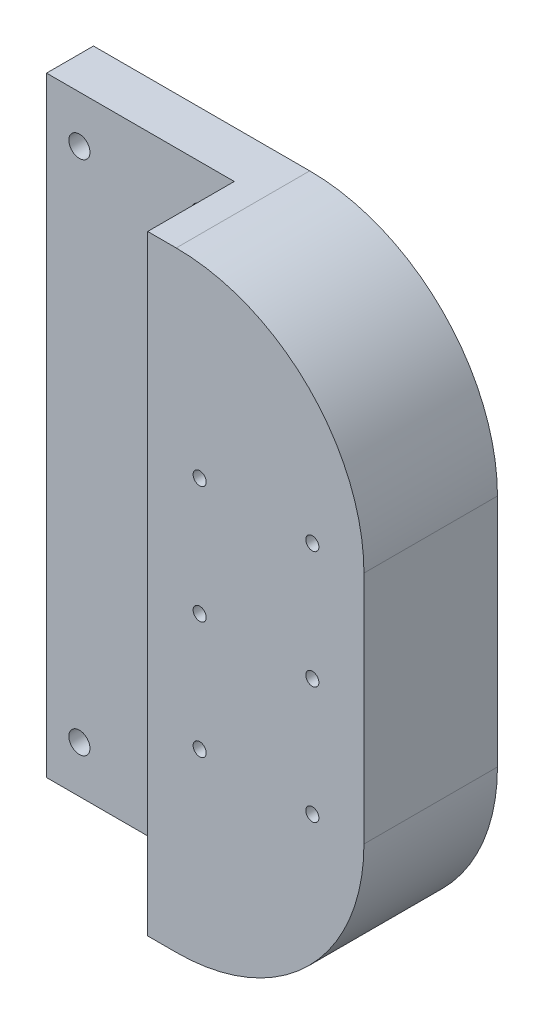
SolidWorks part; units mm, degrees
ref_plane "Front Plane" through (0, 0, 0) normal (0, 0, 1) x (1, 0, 0)
ref_plane "Top Plane" through (0, 0, 0) normal (0, 1, 0) x (1, 0, 0)
ref_plane "Right Plane" through (0, 0, 0) normal (1, 0, 0) x (0, 0, -1)
sketch "Sketch1" plane through (0, 0, 0) normal (0, 0, 1) x (1, 0, 0)
  line L0 (43.042, -25) -> (43.042, 25)
  line L1 (3.042, 65) -> (-3.042, 65)
  line L2 (-3.042, 65) -> (-3.042, -65)
  line L3 (-3.042, -65) -> (3.042, -65)
  line L4 (-3.042, -65) -> (-3.042, 65)
  line L5 (-3.042, 65) -> (-43.042, 65)
  line L6 (-43.042, 65) -> (-43.042, -65)
  line L7 (-43.042, -65) -> (-3.042, -65)
  circle A0 centre (32.0418, 0) radius 1.4
  circle A1 centre (32.0418, -25) radius 1.4
  circle A2 centre (32.0418, 25) radius 1.4
  circle A3 centre (8.0418, 0) radius 1.4
  circle A4 centre (8.0418, 25) radius 1.4
  circle A5 centre (8.0418, -25) radius 1.4
  circle A6 centre (-36.042, 55) radius 2.25
  circle A7 centre (-10.042, -55) radius 2.25
  circle A8 centre (-36.042, -55) radius 2.25
  circle A9 centre (-10.042, 55) radius 2.25
  arc A10 (3.042, -65) -> (43.042, -25) centre (3.042, -25) ccw
  arc A11 (43.042, 25) -> (3.042, 65) centre (3.042, 25) ccw
  dimension "D1" = 4.5
  dimension "D2" = 2.8
  dimension "D3" = 40
  dimension "D4" = 8.0418
  dimension "D5" = 32.0418
  dimension "D6" = 43.042
  dimension "D7" = 3.042
  dimension "D8" = 10.042
  dimension "D9" = 36.042
  dimension "D10" = 43.042
  dimension "D11" = 55
  dimension "D12" = 65
  dimension "D13" = 55
  dimension "D14" = 65
extrude "Boss-Extrude1" add sketch "Sketch1" along normal blind 10 contours L6 L7 L2 L5 A9 A8 A7 A6 | L0 A11 L1 L2 L3 A10 A0 A1 A2 A3 A4 A5 region at (18.1604, 0, 0) region at (-23.042, 0, 0)
extrude "Boss-Extrude2" add sketch "Sketch1<3>" along normal blind 28.45 contours L0 A11 L1 L2 L3 A10 A0 A1 A2 A3 A4 A5 region at (18.1604, 0, 0)
sketch "Sketch1<3>" plane through (0, 0, 0) normal (0, 0, 1) x (1, 0, 0) same geometry as "Sketch1"
